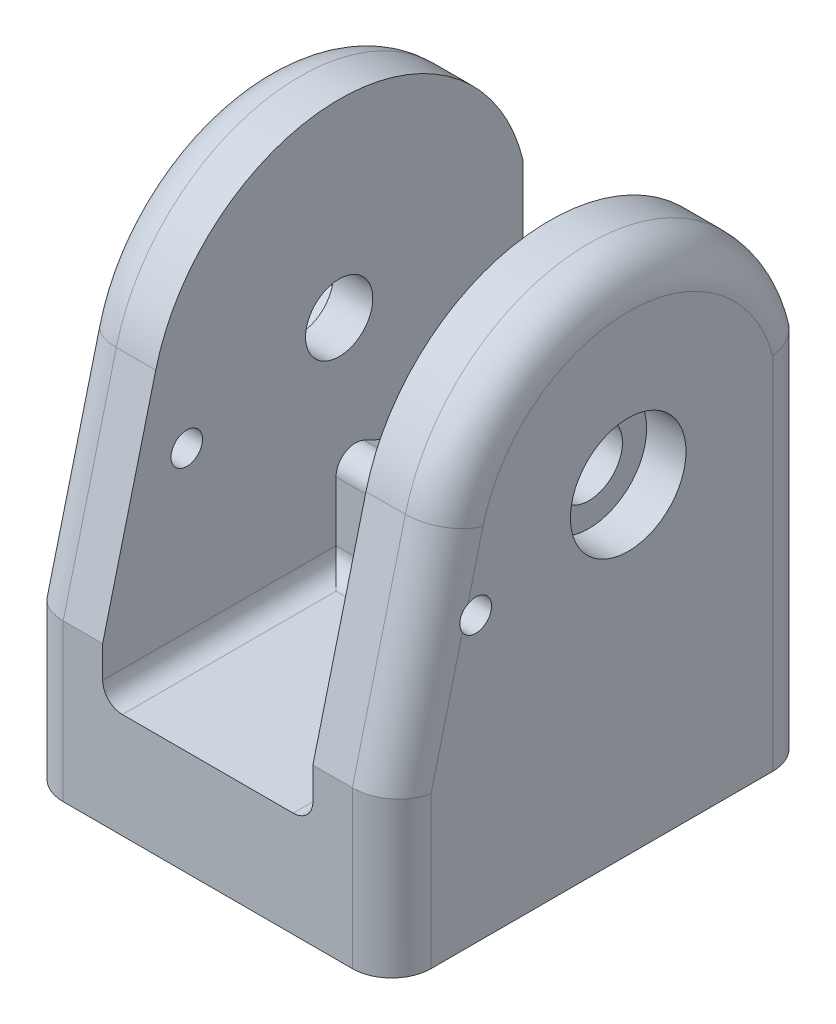
SolidWorks part; units mm, degrees
ref_plane "Front Plane" through (0, 0, 0) normal (0, 0, 1) x (1, 0, 0)
ref_plane "Top Plane" through (0, 0, 0) normal (0, 1, 0) x (1, 0, 0)
ref_plane "Right Plane" through (0, 0, 0) normal (1, 0, 0) x (0, 0, -1)
sketch "Sketch2" plane through (0, 0, 0) normal (0, 1, 0) x (1, 0, 0)
  line L0 (5, 10) -> (8.75, 10)
  line L1 (-8.75, -10) -> (8.75, -10)
  line L2 (-8.75, -10) -> (-8.75, 10)
  line L3 (-8.75, 10) -> (-5, 10)
  line L4 (8.75, -10) -> (8.75, 10)
  line L5 (-8.75, -10) -> (8.75, 10) construction
  line L6 (-8.75, 10) -> (8.75, -10) construction
  line L8 (-5, 10) -> (-5, 5)
  line L9 (-5, 5) -> (5, 5)
  line L10 (5, 10) -> (5, 5)
  point P0 (0, 0)
  point P15 (-5, 5)
  dimension "D1" = 17.5
  dimension "D2" = 20
  dimension "D3" = 3.75
  dimension "D4" = 5
extrude "Boss-Extrude1" add sketch "Sketch2" along normal blind 25
sketch "Sketch3" plane through (0, 25, 0) normal (0, 1, 0) x (1, 0, 0)
  line L0 (-8.75, -10) -> (8.75, -10) construction
  line L1 (-5, 10) -> (5, 10)
  line L2 (-5, 10) -> (-5, -10)
  line L3 (-5, -10) -> (5, -10)
  line L4 (5, 10) -> (5, -10)
  line L5 (5, 10) -> (5, 5) construction
extrude "Cut-Extrude1" cut sketch "Sketch3" against normal blind 20
sketch "Sketch4" plane through (8.75, 0, 0) normal (1, 0, 0) x (0, 0, -1)
  line L0 (10, 25) -> (10, 0) construction
  line L1 (-10, 25) -> (10, 25) construction
  line L2 (10, 17.3565) -> (10, 0)
  line L3 (10, 0) -> (-10, 0)
  line L4 (-10, 0) -> (-10, 7.4522)
  line L6 (-10, 7.4522) -> (-7.4764, 17.4522)
  line L7 (-10, 25) -> (-10, 0) construction
  circle A0 centre (1.25, 15.25) radius 1.6
  arc A1 (10, 17.3565) -> (-7.4764, 17.4522) centre (1.25, 15.25) ccw
  circle A2 centre (-6, 13.5) radius 0.75
  dimension "D1" = 8.75
  dimension "D4" = 3.2
  dimension "D7" = 9
  dimension "D6" = 1.75
  dimension "D8" = 1.5
  dimension "D2" = 9.75
  dimension "D3" = 10
  dimension "D5" = 4
extrude "Cut-Extrude2" cut sketch "Sketch4" against normal through all flip side to cut
fillet "Fillet1" radius 1.875 8 edges at (-8.75, 12.4522, 8.7382) (8.75, 12.4522, 8.7382) (-8.75, 8.6783, -10) (8.75, 8.6783, -10) (-8.75, 3.7261, 10) (8.75, 3.7261, 10) (-8.75, 24.2499, -1.2993) (8.75, 24.2499, -1.2993)
sketch "Sketch7" plane through (8.75, 0, 0) normal (1, 0, 0) x (0, 0, -1)
  line L1 (-10, 0) -> (10, 0)
  line L2 (-10, 0) -> (-10, 25)
  line L3 (-10, 25) -> (10, 25)
  line L4 (10, 0) -> (10, 25)
  dimension "D1" = 25
  dimension "D2" = 20
extrude "Cut-Extrude4" cut sketch "Sketch7" against normal blind 8.75
sketch "Sketch8" plane through (-5, 0, 0) normal (1, 0, 0) x (0, 0, -1)
  line L0 (5, 5) -> (5, 8.4)
  line L2 (5, 8.4) -> (1.1, 10.25)
  line L3 (1.1, 10.25) -> (1.1, 5)
  line L4 (5, 5) -> (-10, 5) construction
  line L5 (1.1, 5) -> (5, 5)
  line L7 (5, 5) -> (5, 0) construction
  dimension "D1" = 3.4
  dimension "D2" = 5.25
  dimension "D3" = 3.9
extrude "Boss-Extrude3" add sketch "Sketch8" along normal up to surface (5 mm away) up to face at (0, 2.5, 2.5)
fillet "Fillet2" radius 0.9375 4 edges at (-2.5, 8.4, -5) (-2.5, 10.25, -1.1) (-2.5, 5, -1.1) (-5, 5, 4.45)
mirror "Mirror2" about plane through (0, 0, 0) normal (-1, 0, 0) of bodies 108
sketch "Sketch11" plane through (8.75, 0, 0) normal (1, 0, 0) x (0, 0, -1)
  circle A0 centre (1.25, 15.25) radius 2.75
  dimension "D1" = 5.5
extrude "Cut-Extrude6" cut sketch "Sketch11" against normal blind 1.875
sketch "Sketch12" plane through (-8.75, 0, 0) normal (-1, 0, 0) x (0, 0, 1)
  line L1 (-1.25, 18.4254) -> (-4, 16.8377)
  line L2 (-4, 16.8377) -> (-4, 13.6623)
  line L3 (-4, 13.6623) -> (-1.25, 12.0746)
  line L4 (-1.25, 12.0746) -> (1.5, 13.6623)
  line L5 (1.5, 13.6623) -> (1.5, 16.8377)
  line L6 (1.5, 16.8377) -> (-1.25, 18.4254)
  circle A0 centre (-1.25, 15.25) radius 2.75 construction
  dimension "D1" = 5.5
extrude "Cut-Extrude7" cut sketch "Sketch12" against normal blind 1.875
sketch "Sketch13" [suppressed] plane through (-8.75, 0, 0) normal (-1, 0, 0) x (0, 0, 1)
  text T0 "I" font "Century Schoolbook" height in points 36
extrude "Boss-Extrude4" [suppressed] add sketch "Sketch13" along normal blind 0.2
sketch "Sketch14" plane through (-8.75, 0, 0) normal (-1, 0, 0) x (0, 0, 1)
  text T0 "M" font "Century Schoolbook" height in points 36
extrude "Boss-Extrude5" add sketch "Sketch14" along normal blind 0.2
sketch "Sketch16" [suppressed] plane through (-8.75, 0, 0) normal (-1, 0, 0) x (0, 0, 1)
  text T0 "R" font "Century Schoolbook" height in points 36
extrude "Boss-Extrude6" [suppressed] add sketch "Sketch16" along normal blind 0.2
sketch "Sketch17" [suppressed] plane through (-8.75, 0, 0) normal (-1, 0, 0) x (0, 0, 1)
  text T0 "P" font "Century Schoolbook" height in points 36
extrude "Boss-Extrude7" [suppressed] add sketch "Sketch17" along normal blind 0.2
sketch "Sketch18" [suppressed] plane through (-8.75, 0, 0) normal (-1, 0, 0) x (0, 0, 1)
  text T0 "T" font "Century Schoolbook" height in points 36
extrude "Boss-Extrude8" [suppressed] add sketch "Sketch18" along normal blind 0.2
